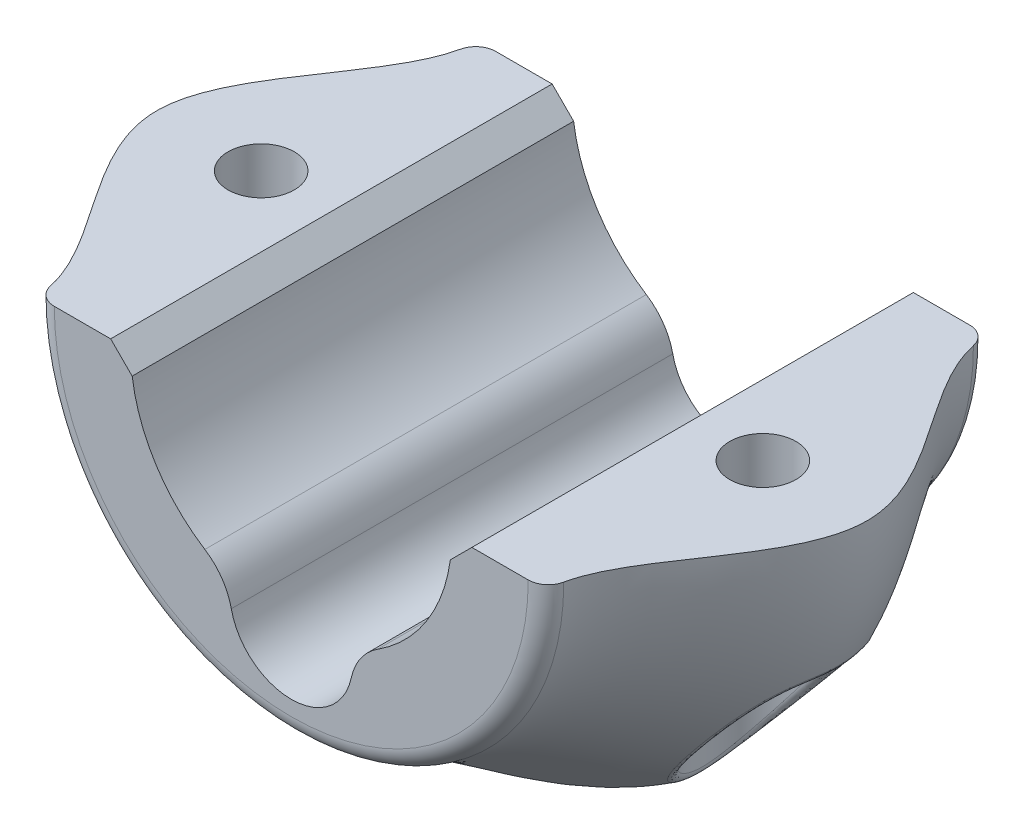
SolidWorks part; units mm, degrees
ref_plane "Ebene vorne" through (0, 0, 0) normal (0, 0, 1) x (1, 0, 0)
ref_plane "Ebene oben" through (0, 0, 0) normal (0, 1, 0) x (1, 0, 0)
ref_plane "Ebene rechts" through (0, 0, 0) normal (1, 0, 0) x (0, 0, -1)
sketch "Skizze1" plane through (0, 0, 0) normal (0, 0, 1) x (1, 0, 0)
  line L0 (-8, 0) -> (-12.7, 0)
  line L1 (8, 0) -> (12.7, 0)
  arc A0 (-8, 0) -> (8, 0) centre (0, 0) ccw
  arc A1 (-12.7, 0) -> (12.7, 0) centre (0, 0) ccw
  dimension "D1" = 8
  dimension "D2" = 12.7
extrude "Aufsatz-Linear austragen1" add sketch "Skizze1" along normal mid plane 22
sketch "Skizze12" plane through (0, 0, 0) normal (0, 1, 0) x (1, 0, 0)
  line L0 (-12.7, 11) -> (-12.7, -11)
  line L1 (-12.7, -14.3025) -> (-12.7, -7.4105) construction
  line L2 (-12.7, 6.8657) -> (-12.7, 16.2182) construction
  line L3 (0, 11) -> (0, -11) construction
  line L4 (8, 11) -> (-8, 11) construction
  line L5 (-8, -11) -> (8, -11) construction
  spline S0 degree 3 poles (-12.7, 11) (-12.7, 7.6667) (-22.7, 0) (-12.7, -7.6667) (-12.7, -11) knots 0 0 0 0 0.5 1 1 1 1
  dimension "D1" = 10
  dimension "D2" = 10
  dimension "D3" = 5
revolve "Rotation2" add sketch "Skizze12" angle 180 about L3
sketch "Skizze13" plane through (0, 0, 0) normal (0, 1, 0) x (1, 0, 0)
  line L0 (0, 11) -> (0, -11) construction
  line L1 (8, 11) -> (-8, 11) construction
  line L2 (-8, -11) -> (8, -11) construction
  circle A0 centre (12.5, 0) radius 1.65
  circle A1 centre (-12.5, 0) radius 1.65
  dimension "D1" = 3.3
  dimension "D2" = 25
extrude "Schnitt-Linear austragen4" cut sketch "Skizze13" against normal up to next
sketch "Skizze14" plane through (0, 0, 0) normal (0, 1, 0) x (1, 0, 0)
  line L8 (0, 11) -> (0, -11) construction
  line L9 (8, 11) -> (-8, 11) construction
  line L10 (-8, -11) -> (8, -11) construction
  circle A0 centre (12.5, 0) radius 3
  circle A2 centre (-12.5, 0) radius 3
  dimension "D1" = 6
extrude "Schnitt-Linear austragen5" cut sketch "Skizze14" against normal up to next from offset 3 offset against normal yes
chamfer "Fase1" distance 1 angle 45 2 edges at (-8, 0, 0) (8, 0, 0)
sketch "Skizze9" plane through (0, 0, 11) normal (0, 0, 1) x (1, 0, 0)
  arc A0 (-3, -7.4162) -> (3, -7.4162) centre (0, -8) ccw
  arc A1 (-7.9278, -1.0722) -> (7.9278, -1.0722) centre (0, 0) ccw construction
  arc A2 (-3, -7.4162) -> (3, -7.4162) centre (0, 0) ccw
  dimension "D1" = 6
extrude "Schnitt-Linear austragen3" cut sketch "Skizze9" against normal up to surface (22 mm away) up to face at (0, -3.6287, -11)
fillet "Verrundung5" radius 3 2 edges at (3, -7.4162, 0) (-3, -7.4162, 0)
fillet "Verrundung7" radius 1 1 edges at (0, -12.7, -11)
fillet "Verrundung8" radius 1 1 edges at (0, -12.7, 11)
fillet "Verrundung9" radius 0.4 2 edges at (-9.5, -14.9345, -0.0002) (15.4935, -8.5491, -0.1972)
equation "\"D2@Skizze1\"=25.4/2"
